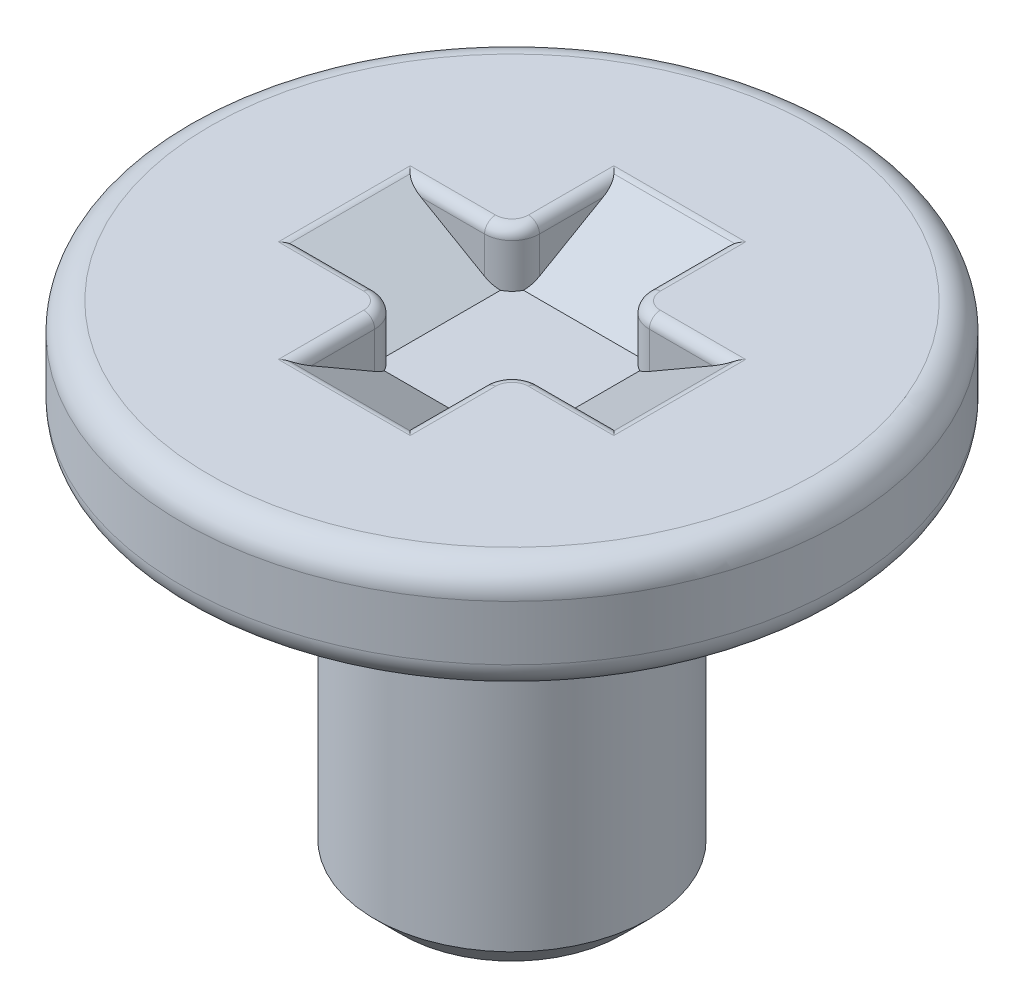
SolidWorks part; units mm, degrees
material "AISI 321 Annealed Stainless Steel (SS)"
ref_plane "Front Plane" through (0, 0, 0) normal (0, 0, 1) x (1, 0, 0)
ref_plane "Top Plane" through (0, 0, 0) normal (0, 1, 0) x (1, 0, 0)
ref_plane "Right Plane" through (0, 0, 0) normal (1, 0, 0) x (0, 0, -1)
sketch "Sketch1" plane through (0, 0, 0) normal (0, 0, 1) x (1, 0, 0)
  line L0 (0, 0) -> (3, 0)
  line L1 (3, 0) -> (3, -1)
  line L2 (3, -1) -> (1.25, -1)
  line L3 (1.25, -1) -> (1.25, -4.5)
  line L4 (1.25, -4.5) -> (0, -4.5)
  line L5 (0, -4.5) -> (0, 0)
  line L6 (0, -217.2459) -> (0, 10645.0503) construction
  dimension "D1" = 3.5
  dimension "D2" = 2.5
  dimension "D3" = 6
  dimension "D4" = 1
revolve "Revolve1" add sketch "Sketch1" angle 360 about L6
sketch "Sketch2" plane through (0, 0, 0) normal (0, 1, 0) x (1, 0, 0)
  line L0 (-0.5, 0.5) -> (-0.5, 1.5)
  line L1 (-0.5, 1.5) -> (0.5, 1.5)
  line L2 (0.5, 1.5) -> (0.5, 0.5)
  line L3 (0.5, 0.5) -> (1.5, 0.5)
  line L4 (1.5, 0.5) -> (1.5, -0.5)
  line L5 (1.5, -0.5) -> (0.5, -0.5)
  line L6 (0.5, -0.5) -> (0.5, -1.5)
  line L7 (0.5, -1.5) -> (-0.5, -1.5)
  line L8 (-0.5, -1.5) -> (-0.5, -0.5)
  line L9 (-0.5, -0.5) -> (-1.5, -0.5)
  line L10 (-1.5, -0.5) -> (-1.5, 0.5)
  line L11 (-1.5, 0.5) -> (-0.5, 0.5)
  line L12 (-0.5, 0.5) -> (0.5, -0.5) construction
  line L13 (0.5, 0.5) -> (-0.5, -0.5) construction
  line L14 (0, 1.5) -> (0, -1.5) construction
  line L15 (1.5, 0) -> (-1.5, 0) construction
  point P9 (0, 0)
  point P13 (0, 0)
  point P19 (0, 0)
  point P20 (0, 0)
  dimension "D1" = 3
  dimension "D2" = 3
  dimension "D3" = 1
extrude "Cut-Extrude1" cut sketch "Sketch2" against normal blind 0.5
chamfer "Chamfer1" distance 0.5 angle 60 4 edges at (-1.5, -0.5, 0) (0, -0.5, 1.5) (1.5, -0.5, 0) (0, -0.5, -1.5) first distance on face at (-1.5, -0.25, 0) first distance on face at (0, -0.25, 1.5) first distance on face at (1.5, -0.25, 0) first distance on face at (0, -0.25, -1.5)
fillet "Fillet1" radius 0.25 4 edges at (-0.5, -0.25, 0.5) (-0.5, -0.25, -0.5) (0.5, -0.25, 0.5) (0.5, -0.25, -0.5)
fillet "Fillet2" radius 0.1 16 edges at (1.125, 0, -0.5) (0.5732, 0, -0.5732) (-0.5, 0, -1.125) (-0.5732, 0, -0.5732) (-1.125, 0, 0.5) (-0.5732, 0, 0.5732) (0.5, 0, 1.125) (0.5732, 0, 0.5732) (0.5, 0, -1.125) (1.5, 0, 0) (0, 0, -1.5) (-1.125, 0, -0.5) (-1.5, 0, 0) (-0.5, 0, 1.125) (0, 0, 1.5) (1.125, 0, 0.5)
fillet "Fillet3" radius 0.25 2 edges at (3, 0, 0) (3, -1, 0)
chamfer "Chamfer2" distance 0.25 angle 45 1 edges at (1.25, -4.5, 0)
